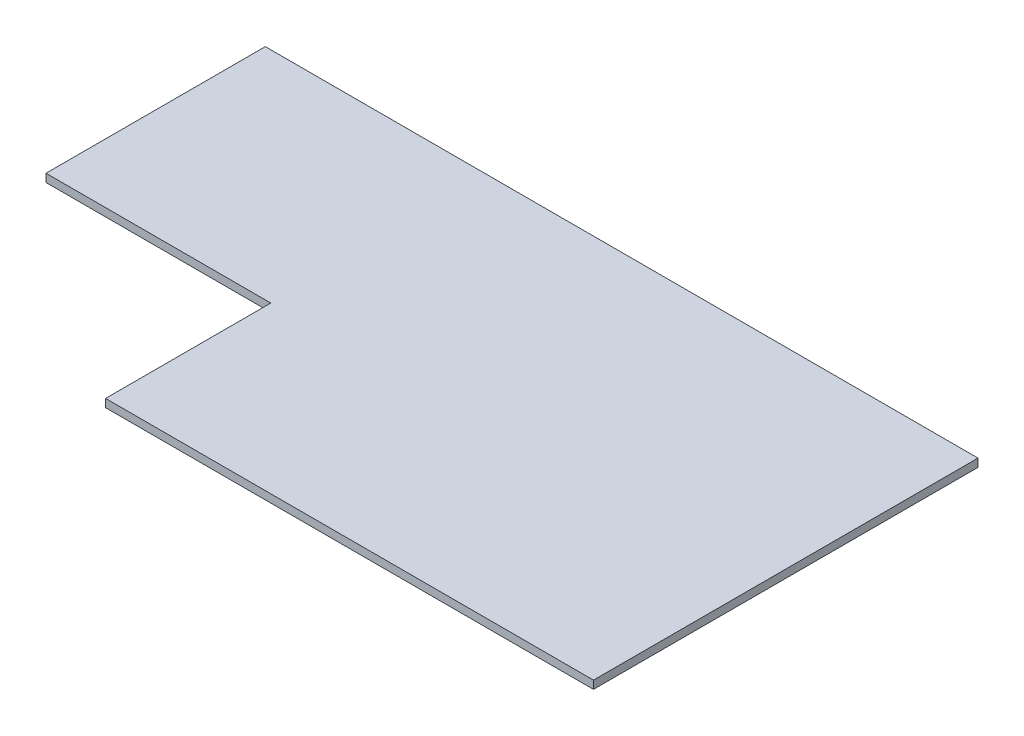
SolidWorks part; units mm, degrees
material "Acrylic (Medium-high impact)"
ref_plane "Front Plane" through (0, 0, 0) normal (0, 0, 1) x (1, 0, 0)
ref_plane "Top Plane" through (0, 0, 0) normal (0, 1, 0) x (1, 0, 0)
ref_plane "Right Plane" through (0, 0, 0) normal (1, 0, 0) x (0, 0, -1)
sketch "Sketch1" plane through (0, 0, 0) normal (0, 1, 0) x (1, 0, 0)
  line L1 (-94.7678, -156.4891) -> (290.0422, -156.4891)
  line L2 (-272.0598, -26.1871) -> (-272.0598, 146.7869)
  line L3 (-272.0598, 146.7869) -> (290.0422, 146.7869)
  line L4 (290.0422, -156.4891) -> (290.0422, 146.7869)
  line L5 (-289.8578, -146.6936) -> (290.0422, 146.7869) construction
  line L6 (-272.0598, 146.7869) -> (290.0422, -156.4891) construction
  line L9 (-272.0598, -26.1871) -> (-94.7678, -26.1871)
  line L10 (-94.7678, -156.4891) -> (-94.7678, -26.1871)
  point P0 (0, 0)
  dimension "D1" = 562.102
  dimension "D2" = 303.276
  dimension "D3" = 177.292
  dimension "D4" = 130.302
extrude "Boss-Extrude1" add sketch "Sketch1" along normal mid plane 6.35
